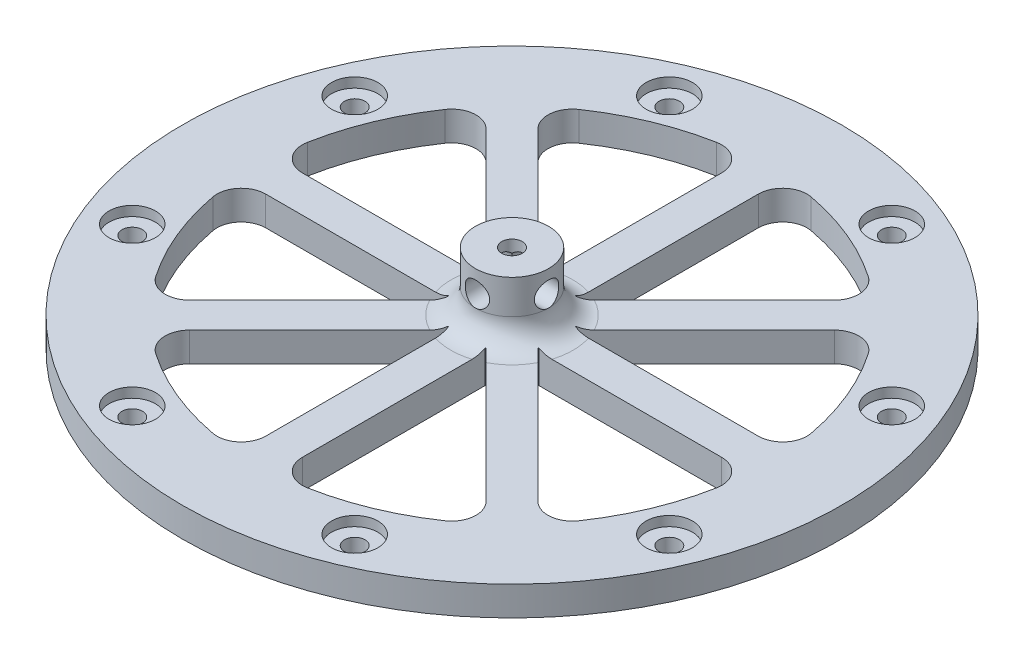
SolidWorks part; units mm, degrees
ref_plane "Front Plane" through (0, 0, 0) normal (0, 0, 1) x (1, 0, 0)
ref_plane "Top Plane" through (0, 0, 0) normal (0, 1, 0) x (1, 0, 0)
ref_plane "Right Plane" through (0, 0, 0) normal (1, 0, 0) x (0, 0, -1)
sketch "Sketch1" plane through (0, 0, 0) normal (0, 1, 0) x (1, 0, 0)
  line L16 (3.75, 9.2702) -> (3.75, 52.3659)
  line L17 (3.9034, 9.2067) -> (34.3766, 39.6799)
  line L18 (-3.9034, 9.2067) -> (-34.3766, 39.6799)
  line L19 (-3.75, 9.2702) -> (-3.75, 52.3659)
  line L20 (-9.2702, 3.75) -> (-52.3659, 3.75)
  line L21 (-9.2067, 3.9034) -> (-39.6799, 34.3766)
  line L22 (-9.2067, -3.9034) -> (-39.6799, -34.3766)
  line L23 (-9.2702, -3.75) -> (-52.3659, -3.75)
  line L24 (-3.75, -9.2702) -> (-3.75, -52.3659)
  line L25 (-3.9034, -9.2067) -> (-34.3766, -39.6799)
  line L26 (3.9034, -9.2067) -> (34.3766, -39.6799)
  line L27 (3.75, -9.2702) -> (3.75, -52.3659)
  line L28 (9.2702, -3.75) -> (52.3659, -3.75)
  line L29 (9.2067, -3.9034) -> (39.6799, -34.3766)
  line L30 (9.2067, 3.9034) -> (39.6799, 34.3766)
  line L31 (9.2702, 3.75) -> (52.3659, 3.75)
  circle A0 centre (0, 0) radius 67.5
  arc A1 (-3.75, 52.3659) -> (-34.3766, 39.6799) centre (0, 0) ccw
  arc A2 (3.9034, 9.2067) -> (3.75, 9.2702) centre (0, 0) ccw
  arc A3 (-39.6799, 34.3766) -> (-52.3659, 3.75) centre (0, 0) ccw
  arc A4 (-52.3659, -3.75) -> (-39.6799, -34.3766) centre (0, 0) ccw
  arc A5 (-34.3766, -39.6799) -> (-3.75, -52.3659) centre (0, 0) ccw
  arc A6 (3.75, -52.3659) -> (34.3766, -39.6799) centre (0, 0) ccw
  arc A7 (39.6799, -34.3766) -> (52.3659, -3.75) centre (0, 0) ccw
  arc A8 (52.3659, 3.75) -> (39.6799, 34.3766) centre (0, 0) ccw
  arc A9 (34.3766, 39.6799) -> (3.75, 52.3659) centre (0, 0) ccw
  arc A10 (-9.2067, 3.9034) -> (-9.2702, 3.75) centre (0, 0) ccw
  arc A11 (-3.75, 9.2702) -> (-3.9034, 9.2067) centre (0, 0) ccw
  arc A12 (-3.9034, -9.2067) -> (-3.75, -9.2702) centre (0, 0) ccw
  arc A13 (3.75, -9.2702) -> (3.9034, -9.2067) centre (0, 0) ccw
  arc A14 (-9.2702, -3.75) -> (-9.2067, -3.9034) centre (0, 0) ccw
  arc A15 (9.2702, 3.75) -> (9.2067, 3.9034) centre (0, 0) ccw
  arc A16 (9.2067, -3.9034) -> (9.2702, -3.75) centre (0, 0) ccw
  point P39 (0, 0)
  dimension "D1" = 135
  dimension "D2" = 105
  dimension "D5" = 20
extrude "Boss-Extrude1" add sketch "Sketch1" along normal mid plane 6
sketch "Sketch2" plane through (0, 3, 0) normal (0, 1, 0) x (1, 0, 0)
  line L0 (0, 0) -> (-127.1671, 0) construction
  line L1 (0, 0) -> (-113.7342, 47.1103) construction
  circle A0 centre (-55, 22.7817) radius 4.75
  circle A1 centre (-22.7817, 55) radius 4.75
  circle A2 centre (22.7817, 55) radius 4.75
  circle A3 centre (55, 22.7817) radius 4.75
  circle A4 centre (55, -22.7817) radius 4.75
  circle A5 centre (22.7817, -55) radius 4.75
  circle A6 centre (-22.7817, -55) radius 4.75
  circle A7 centre (-55, -22.7817) radius 4.75
  point P23 (0, 0)
  dimension "D1" = 9.5
  dimension "D2" = 22.5
  dimension "D4" = 55
  dimension "D3" = 8
extrude "Cut-Extrude1" cut sketch "Sketch2" against normal blind 2
sketch "Sketch3" plane through (0, 1, 0) normal (0, 1, 0) x (1, 0, 0)
  circle A0 centre (-55, 22.7817) radius 2.1
  circle A1 centre (-22.7817, 55) radius 2.1
  circle A2 centre (22.7817, 55) radius 2.1
  circle A3 centre (55, 22.7817) radius 2.1
  circle A4 centre (55, -22.7817) radius 2.1
  circle A5 centre (22.7817, -55) radius 2.1
  circle A6 centre (-22.7817, -55) radius 2.1
  circle A7 centre (-55, -22.7817) radius 2.1
  point P20 (0, 0)
  dimension "D1" = 4.2
  dimension "D2" = 8
extrude "Cut-Extrude2" cut sketch "Sketch3" against normal up to surface (4 mm away) up to face at (28.251, -3, -11.7019)
sketch "Sketch4" plane through (0, 3, 0) normal (0, 1, 0) x (1, 0, 0)
  circle A0 centre (0, 0) radius 7.5
  dimension "D1" = 15
extrude "Boss-Extrude2" add sketch "Sketch4" along normal blind 12
sketch "Sketch5" plane through (0, 15, 0) normal (0, 1, 0) x (1, 0, 0)
  circle A0 centre (0, 0) radius 2.1
  dimension "D1" = 4.2
extrude "Cut-Extrude3" cut sketch "Sketch5" against normal up to surface (18 mm away) up to face at (-22.7817, -3, -52.9)
fillet "Fillet3" radius 5 1 edges at (0, 3, 7.5)
sketch "Sketch6" plane through (0, 0, 0) normal (1, 0, 0) x (0, 0, -1)
  line L0 (0, 9.9) -> (0, -9.9) construction
  line L1 (2.1, 15) -> (-2.1, 15) construction
  circle A0 centre (0, 10.5) radius 2.5
  dimension "D1" = 5
  dimension "D2" = 4.5
extrude "Cut-Extrude4" cut sketch "Sketch6" along normal mid plane 20
fillet "Fillet2" radius 5 16 edges at (-52.3659, 0, -3.75) (52.3659, 0, -3.75) (-39.6799, 0, 34.3766) (52.3659, 0, 3.75) (34.3766, 0, 39.6799) (-3.75, 0, 52.3659) (39.6799, 0, 34.3766) (3.75, 0, 52.3659) (-34.3766, 0, 39.6799) (-52.3659, 0, 3.75) (-39.6799, 0, -34.3766) (-34.3766, 0, -39.6799) (-3.75, 0, -52.3659) (3.75, 0, -52.3659) (39.6799, 0, -34.3766) (34.3766, 0, -39.6799)
sketch "Sketch7" plane through (0, 0, 0) normal (0, 0, 1) x (1, 0, 0)
  line L0 (0, -9.9) -> (0, 9.9) construction
  line L1 (7.5, 15) -> (-7.5, 15) construction
  circle A0 centre (0, 10.5) radius 2.5
  dimension "D1" = 5
  dimension "D2" = 4.5
extrude "Cut-Extrude5" cut sketch "Sketch7" against normal mid plane 20
